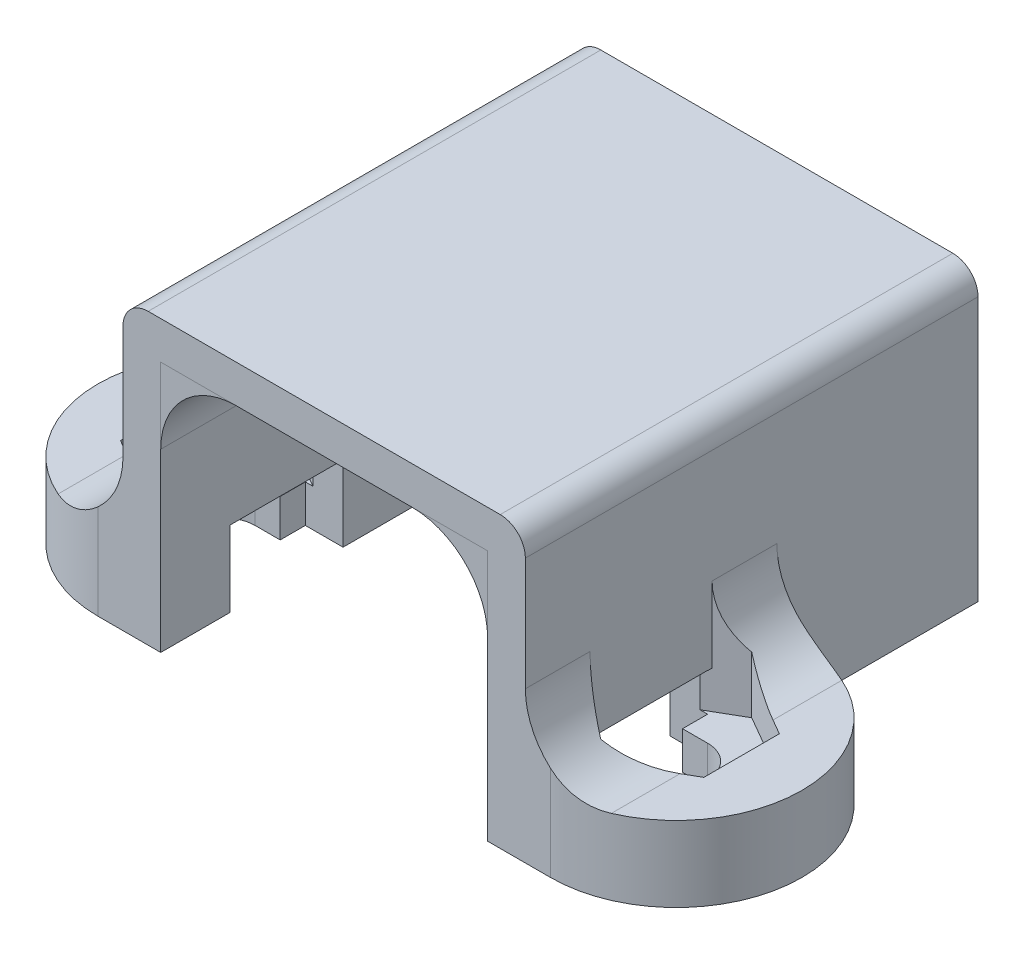
SolidWorks part; units mm, degrees
material "PE haute densité"
ref_plane "Plan de face" through (0, 0, 0) normal (0, 0, 1) x (1, 0, 0)
ref_plane "Plan de dessus" through (0, 0, 0) normal (0, 1, 0) x (1, 0, 0)
ref_plane "Plan de droite" through (0, 0, 0) normal (1, 0, 0) x (0, 0, -1)
sketch "Esquisse1" plane through (0, 0, 0) normal (0, 0, 1) x (1, 0, 0)
  line L0 (0, 13.7019) -> (0, -5.943) construction
  line L1 (-8, 0) -> (-8, 11.5)
  line L2 (-8, 11.5) -> (8, 11.5)
  line L3 (8, 11.5) -> (8, 0)
  line L4 (-8, 0) -> (-6.5, 0)
  line L5 (-6.5, 0) -> (-6.5, 10)
  line L6 (-6.5, 10) -> (6.5, 10)
  line L7 (6.5, 10) -> (6.5, 0)
  line L8 (6.5, 0) -> (8, 0)
  dimension "D1" = 16
  dimension "D2" = 11.5
  dimension "D3" = 13
  dimension "D4" = 10
extrude "Boss.-Extru.1" add sketch "Esquisse1" along normal blind 5 and the other way blind 13
sketch "Esquisse2" plane through (0, 0, 0) normal (0, -1, 0) x (1, 0, 0)
  line L0 (-12.707, 0) -> (11.545, 0) construction
  line L3 (-8, 5) -> (-8, -5)
  line L4 (-8, 5) -> (-9, 5)
  line L5 (-9, -5) -> (-8, -5)
  line L6 (-9, 5.4734) -> (-9, -5.4734) construction
  line L7 (-8, -13) -> (-8, 5) construction
  line L8 (0, -14.8539) -> (0, 0) construction
  line L9 (9, -5) -> (8, -5)
  line L10 (8, 5) -> (8, -5)
  line L11 (8, 5) -> (9, 5)
  arc A0 (-9, 5) -> (-9, -5) centre (-9, 0) ccw
  arc A1 (9, 5) -> (9, -5) centre (9, 0) cw
  dimension "D1" = 9
  dimension "D2" = 5
extrude "Boss.-Extru.2" add sketch "Esquisse2" against normal blind 3
sketch "Esquisse3" plane through (0, 0, 0) normal (0, -1, 0) x (1, 0, 0)
  line L0 (-9, -6.3161) -> (-9, 6.3161) construction
  line L1 (-15.2134, 0) -> (15.3349, 0) construction
  line L2 (-9, 1.25) -> (-8, 1.25)
  line L3 (0, -4.2429) -> (0, 5.9297) construction
  line L4 (-8, -1.25) -> (-9, -1.25)
  line L5 (-8, -1.25) -> (-8, -2.25)
  line L6 (-8, 1.25) -> (-8, 2.25)
  line L7 (-8, 2.25) -> (-6.4983, 2.25)
  line L8 (-8, -2.25) -> (-6.5, -2.25)
  line L9 (-6.5, -13) -> (-6.5, 5) construction
  line L10 (-6.4983, 2.25) -> (-6.5, -2.25)
  arc A0 (-9, 1.25) -> (-9, -1.25) centre (-9, 0) ccw
  dimension "D1" = 2.5
  dimension "D2" = 1.5
  dimension "D3" = 4.5
extrude "Enlèv. mat.-Extru.7" cut sketch "Esquisse3" against normal blind 3.01
sketch "Esquisse4" plane through (0, 3, 0) normal (0, 1, 0) x (1, 0, 0)
  line L0 (2.49, 0) -> (-15.3652, 0) construction
  line L1 (-9, 6.3903) -> (-9, -6.3903) construction
  line L3 (-9, 3.0022) -> (-11.6, 1.5011)
  line L4 (-11.6, 1.5011) -> (-11.6, -1.5011)
  line L5 (-11.6, -1.5011) -> (-9, -3.0022)
  line L6 (-9, -3.0022) -> (-6.4, -1.5011)
  line L7 (-6.4, -1.5011) -> (-6.4, 1.5011)
  line L8 (-6.4, 1.5011) -> (-9, 3.0022)
  circle A0 centre (-9, 0) radius 2.6 construction
  dimension "D1" = 9
  dimension "D2" = 5.2
extrude "Enlèv. mat.-Extru.8" cut sketch "Esquisse4" against normal blind 1.5
mirror "Symétrie1" about plane through (0, 0, 0) normal (1, 0, 0) of "Enlèv. mat.-Extru.8", "Enlèv. mat.-Extru.7"
fillet "Congé1" radius 3 4 edges
fillet "Congé2" radius 1 2 edges at (8, 11.5, -4) (-8, 11.5, -4)
sketch "Esquisse5" plane through (0, 0, 5) normal (0, 0, 1) x (1, 0, 0)
  line L0 (-6.5, 10) -> (6.5, 10) construction
  line L1 (-6.5, 0) -> (-6.5, 10) construction
  line L2 (-6.5, 7) -> (-6.5, 10)
  line L3 (-6.5, 10) -> (-3.5, 10)
  line L4 (6.5, 10) -> (6.5, 0) construction
  line L5 (3.5, 10) -> (6.5, 10)
  line L6 (6.5, 10) -> (6.5, 7)
  arc A0 (-3.5, 10) -> (-6.5, 7) centre (-3.5, 7) ccw
  arc A1 (6.5, 7) -> (3.5, 10) centre (3.5, 7) ccw
  dimension "D1" = 6
  dimension "D2" = 6
extrude "Boss.-Extru.3" add sketch "Esquisse5" against normal blind 8 separate body
ref_plane "Plan1" through (0, 0, -5) normal (0, 0, 1) x (1, 0, 0)
ref_plane "Plan2" through (0, 0, -8) normal (0, 0, 1) x (1, 0, 0)
sketch "Esquisse6" plane through (0, 0, -5) normal (0, 0, 1) x (1, 0, 0)
  line L0 (-6.5, 7) -> (-6.25, 7)
  line L1 (-6.5, 0) -> (-6.5, 10) construction
  line L2 (-6.25, 7) -> (-6.25, 8.25)
  line L3 (-4.75, 9.75) -> (-3.5, 9.75)
  line L4 (-3.5, 9.75) -> (-3.5, 10)
  line L5 (-6.5, 10) -> (6.5, 10) construction
  line L6 (-3.5, 10) -> (-6.5, 10)
  line L7 (-6.5, 7) -> (-6.5, 10)
  arc A0 (-6.25, 8.25) -> (-4.75, 9.75) centre (-4.75, 8.25) cw
  dimension "D5" = 1.5
  dimension "D1" = 3
  dimension "D2" = 3
  dimension "D3" = 0.25
  dimension "D4" = 0.25
extrude "Boss.-Extru.4" add sketch "Esquisse6" against normal blind 2
sketch "Esquisse7" plane through (0, 0, -8) normal (0, 0, 1) x (1, 0, 0)
  line L0 (-4.75, 9.75) -> (-3.5, 9.75) construction
  line L1 (-6.25, 7) -> (-6.25, 8.25) construction
  line L2 (-6.5, 10) -> (-6.5, 7) construction
  line L3 (-3.5, 10) -> (-6.5, 10) construction
  line L4 (-6.5, 7) -> (-6.25, 7) construction
  line L5 (-3.5, 9.75) -> (-3.5, 10) construction
  line L6 (-4.75, 9.75) -> (-3.5, 9.75)
  line L7 (-6.25, 7) -> (-6.25, 8.25)
  line L8 (-6.5, 10) -> (-6.5, 7)
  line L9 (-3.5, 10) -> (-6.5, 10)
  line L10 (-6.5, 7) -> (-6.25, 7)
  line L11 (-3.5, 9.75) -> (-3.5, 10)
  arc A0 (-4.75, 9.75) -> (-6.25, 8.25) centre (-4.75, 8.25) ccw construction
  arc A1 (-4.75, 9.75) -> (-6.25, 8.25) centre (-4.75, 8.25) ccw
extrude "Boss.-Extru.5" add sketch "Esquisse7" against normal blind 4
